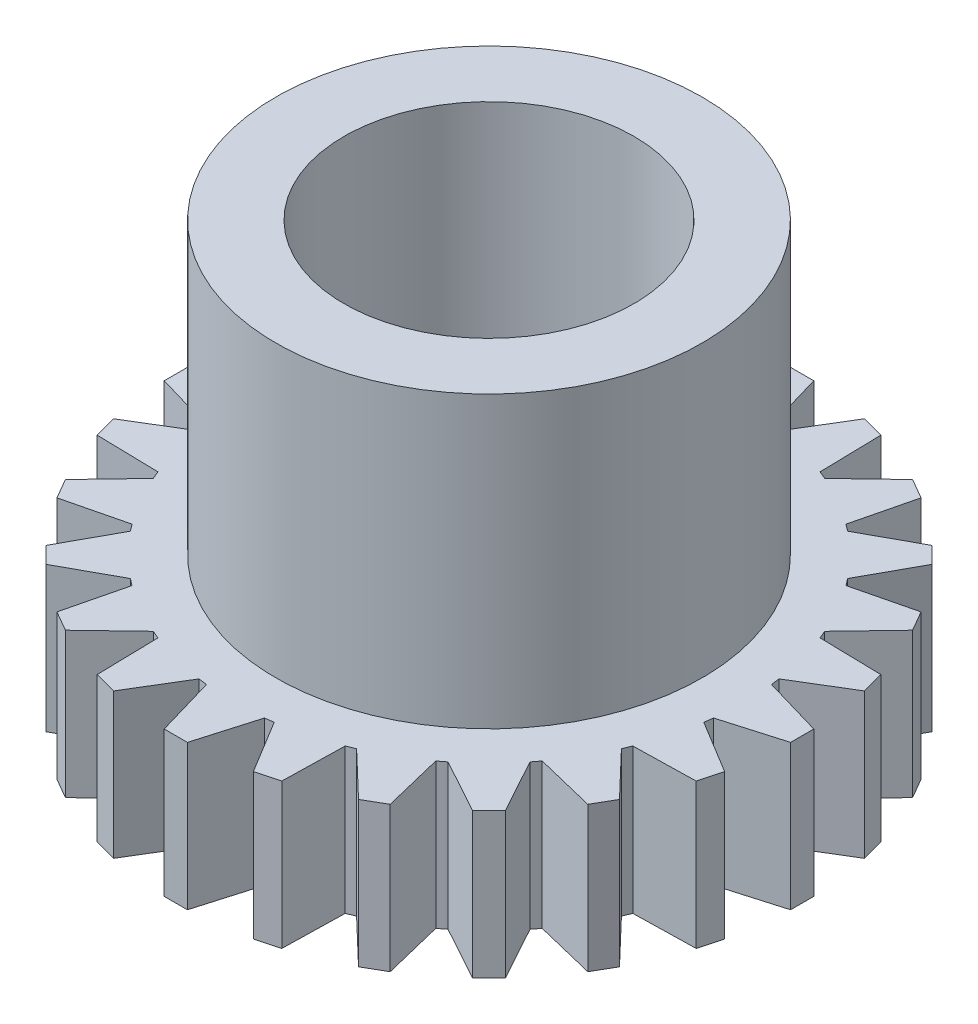
SolidWorks part; units mm, degrees
ref_plane "Front Plane" through (0, 0, 0) normal (0, 0, 1) x (1, 0, 0)
ref_plane "Top Plane" through (0, 0, 0) normal (0, 1, 0) x (1, 0, 0)
ref_plane "Right Plane" through (0, 0, 0) normal (1, 0, 0) x (0, 0, -1)
sketch "Sketch1" plane through (0, 0, 0) normal (0, 1, 0) x (1, 0, 0)
  circle A0 centre (0, 0) radius 3.175
  circle A1 centre (0, 0) radius 4.6672
  dimension "D1" = 6.35
  dimension "D2" = 9.3345
extrude "Boss-Extrude1" add sketch "Sketch1" along normal blind 9.525 contours A1 A0 region at (-4.5352, 0, 0)
sketch "Sketch2" plane through (0, 0, 0) normal (0, 1, 0) x (1, 0, 0)
  line L0 (0, 0) -> (0, 5.588) construction
  line L1 (-0.635, 5.5518) -> (0.635, 5.5518)
  line L2 (0, 5.588) -> (0, 6.858) construction
  line L3 (-0.254, 6.858) -> (0.254, 6.858)
  line L4 (-0.254, 6.858) -> (-0.635, 5.5518)
  line L5 (0.254, 6.858) -> (0.635, 5.5518)
  circle A0 centre (0, 0) radius 5.588
  point P11 (0, 6.858)
  dimension "D1" = 11.176
  dimension "D2" = 1.27
  dimension "D3" = 1.27
  dimension "D4" = 0.508
extrude "Boss-Extrude2" add sketch "Sketch2" along normal blind 3.175 contours L1 A0 region at (0, 0, 0.0017)
extrude "Boss-Extrude3" add sketch "Sketch2<3>" along normal blind 3.175 contours L5 L1 L4 L3
sketch "Sketch2<3>" plane through (0, 0, 0) normal (0, 1, 0) x (1, 0, 0) same geometry as "Sketch2"
pattern_circular "CirPattern1" count 24 over 360 about axis through (0, 9.525, 0) along (0, -1, 0) of "Boss-Extrude3" reverse direction yes
equation "\"Number_Teeth\"= 24"
equation "\"Diametral_Pitch\"= 48"
equation "\"Pitch_Diameter\"= \"Number_Teeth\" * \"1_inch\" / \"Diametral_Pitch\""
equation "\"Tooth_Height\"= .05in"
equation "\"Addendum\"= \"Tooth_Height\" * .4"
equation "\"Dedendum\"= \"Tooth_Height\" * .6"
equation "\"D1@Sketch2\"=\"Pitch_Diameter\"-(2*\"Dedendum\")"
equation "\"D3@Sketch2\"=\"Tooth_Height\""
equation "\"1_inch\"= 1in"
equation "\"D1@CirPattern1\"=\"Number_Teeth\""
